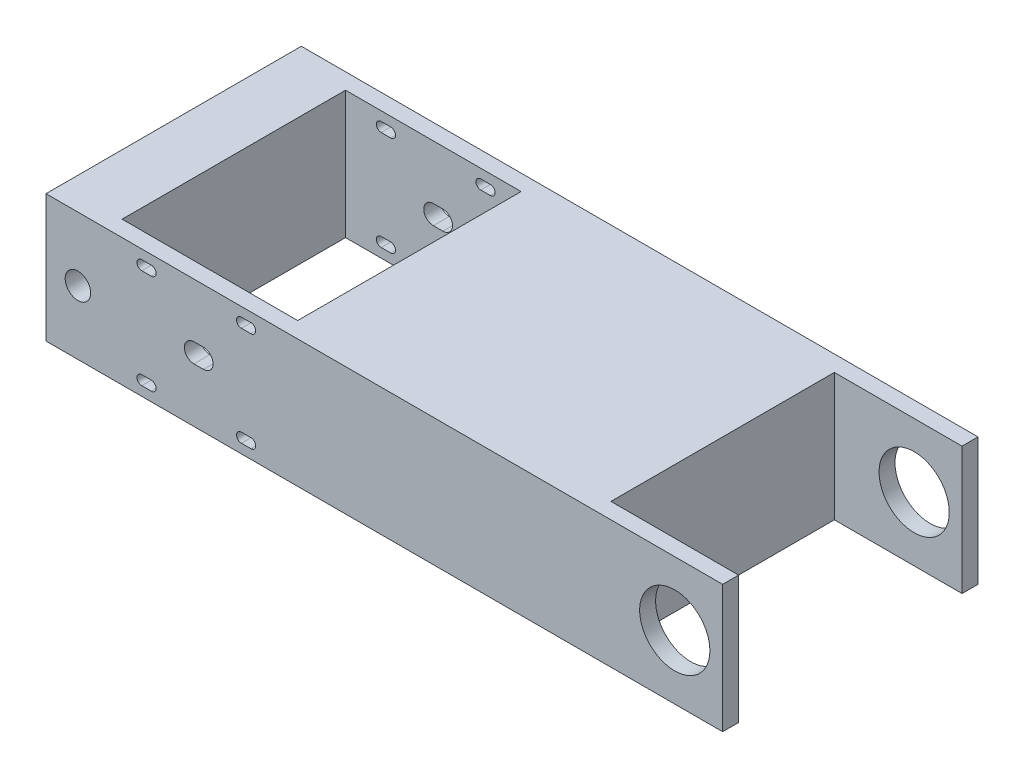
SolidWorks part; units mm, degrees
ref_plane "Front Plane" through (0, 0, 0) normal (0, 0, 1) x (1, 0, 0)
ref_plane "Top Plane" through (0, 0, 0) normal (0, 1, 0) x (1, 0, 0)
ref_plane "Right Plane" through (0, 0, 0) normal (1, 0, 0) x (0, 0, -1)
sketch "Sketch1" plane through (0, 0, 0) normal (0, 0, 1) x (1, 0, 0)
  line L0 (-106, -20) -> (-106, 20)
  line L1 (-106, 20) -> (106, 20)
  line L3 (-106, -20) -> (106, -20)
  line L4 (106, 20) -> (106, -20)
  line L5 (-106, 20) -> (106, -20) construction
  line L6 (-106, -20) -> (106, 20) construction
  line L7 (-76, 15.6) -> (-76, -15.6) construction
  line L8 (-76, 15.6) -> (-43.3, 15.6)
  line L9 (-76, 15.6) -> (-73, 15.6) construction
  line L10 (-76, 17.1) -> (-73, 17.1)
  line L11 (-76, 14.1) -> (-73, 14.1)
  line L12 (-44.8, 15.6) -> (-41.8, 15.6) construction
  line L13 (-44.8, 17.1) -> (-41.8, 17.1)
  line L14 (-44.8, 14.1) -> (-41.8, 14.1)
  line L15 (-76, -15.6) -> (-73, -15.6) construction
  line L16 (-76, -14.1) -> (-73, -14.1)
  line L17 (-76, -17.1) -> (-73, -17.1)
  line L18 (-44.8, -15.6) -> (-41.8, -15.6) construction
  line L19 (-44.8, -14.1) -> (-41.8, -14.1)
  line L20 (-44.8, -17.1) -> (-41.8, -17.1)
  line L21 (-59.65, 0) -> (-56.65, 0) construction
  line L22 (-59.65, 3) -> (-56.65, 3)
  line L23 (-59.65, -3) -> (-56.65, -3)
  circle A0 centre (-96, 0) radius 4
  circle A1 centre (-76, 15.6) radius 1.5 construction
  circle A2 centre (-44.8, 15.6) radius 1.5 construction
  circle A3 centre (-76, -15.6) radius 1.5 construction
  circle A4 centre (-44.8, -15.6) radius 1.5 construction
  circle A5 centre (-59.65, 0) radius 3 construction
  circle A6 centre (91, 0) radius 11
  arc A7 (-76, 17.1) -> (-76, 14.1) centre (-76, 15.6) ccw
  arc A8 (-73, 14.1) -> (-73, 17.1) centre (-73, 15.6) ccw
  arc A9 (-44.8, 17.1) -> (-44.8, 14.1) centre (-44.8, 15.6) ccw
  arc A10 (-41.8, 14.1) -> (-41.8, 17.1) centre (-41.8, 15.6) ccw
  arc A11 (-76, -14.1) -> (-76, -17.1) centre (-76, -15.6) ccw
  arc A12 (-73, -17.1) -> (-73, -14.1) centre (-73, -15.6) ccw
  arc A13 (-44.8, -14.1) -> (-44.8, -17.1) centre (-44.8, -15.6) ccw
  arc A14 (-41.8, -17.1) -> (-41.8, -14.1) centre (-41.8, -15.6) ccw
  arc A15 (-59.65, 3) -> (-59.65, -3) centre (-59.65, 0) ccw
  arc A16 (-56.65, -3) -> (-56.65, 3) centre (-56.65, 0) ccw
  point P0 (0, 0)
  point P16 (-76, 0)
  point P22 (-74.5, 15.6)
  point P28 (-43.3, 15.6)
  point P34 (-74.5, -15.6)
  point P40 (-43.3, -15.6)
  point P46 (-59.65, 15.6)
  point P47 (-58.15, 0)
  dimension "D3" = 8
  dimension "D5" = 31.2
  dimension "D1" = 3
  dimension "D7" = 31.2
  dimension "D9" = 6
  dimension "D10" = 22
  dimension "D4" = 10
  dimension "D2" = 212
  dimension "D6" = 40
  dimension "D8" = 20
  dimension "D11" = 15
  dimension "D12" = 1.5
extrude "Boss-Extrude1" add sketch "Sketch1" along normal mid plane 80 contours L4 L1 L0 L3 A14 L20 A13 L19 A12 L17 A11 L16 A10 L14 A9 A8 L11 A7 L10 L13 A6 A5 A0 region at (-2.9336, 0, 0)
sketch "Sketch2" plane through (0, 0, 0) normal (0, 1, 0) x (1, 0, 0)
  line L0 (-106, 40) -> (106, 40) construction
  line L1 (-87.15, 35) -> (-32.15, 35)
  line L2 (-87.15, 35) -> (-87.15, -35)
  line L3 (-87.15, -35) -> (-32.15, -35)
  line L4 (-32.15, 35) -> (-32.15, -35)
  line L5 (-87.15, 35) -> (-32.15, -35) construction
  line L6 (-87.15, -35) -> (-32.15, 35) construction
  line L8 (106, -40) -> (106, 40) construction
  line L9 (66, 35) -> (106, 35)
  line L10 (66, 35) -> (66, -35)
  line L11 (66, -35) -> (106, -35)
  line L12 (106, 35) -> (106, -35)
  line L13 (66, 35) -> (106, -35) construction
  line L14 (66, -35) -> (106, 35) construction
  point P0 (-59.65, 0)
  point P11 (86, 0)
  dimension "D1" = 55
  dimension "D2" = 5
  dimension "D3" = 59.65
  dimension "D4" = 40
extrude "Cut-Extrude3" cut sketch "Sketch2" against normal through all both and the other way through all
